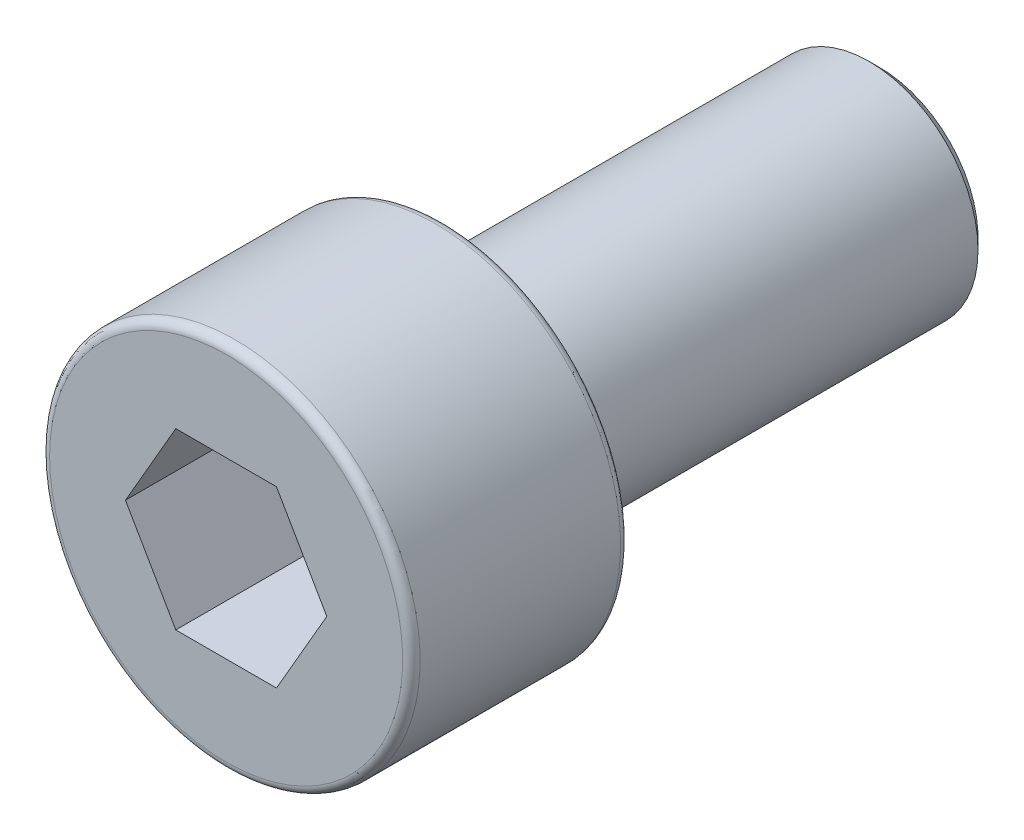
SolidWorks part; units mm, degrees
ref_plane "Front Plane" through (0, 0, 0) normal (0, 0, 1) x (1, 0, 0)
ref_plane "Top Plane" through (0, 0, 0) normal (0, 1, 0) x (1, 0, 0)
ref_plane "Right Plane" through (0, 0, 0) normal (1, 0, 0) x (0, 0, -1)
ref_plane "Plane1" through (0, 0, 15) normal (0, 0, 1) x (1, 0, 0)
sketch "Sketch1" plane through (0, 0, 15) normal (0, 0, 1) x (1, 0, 0)
  circle A0 centre (0, 0) radius 4.25
extrude "Boss-Extrude1" add sketch "Sketch1" against normal blind 5
sketch "Sketch2" plane through (0, 0, 10) normal (0, 0, -1) x (-1, 0, 0)
  circle A0 centre (0, 0) radius 2.5
extrude "Boss-Extrude2" add sketch "Sketch2" along normal blind 10
sketch "Sketch3" plane through (0, 0, 15) normal (0, 0, 1) x (1, 0, 0)
  line L0 (-2.3094, 0) -> (-1.1547, -2)
  line L1 (-1.1547, -2) -> (1.1547, -2)
  line L2 (1.1547, -2) -> (2.3094, 0)
  line L3 (2.3094, 0) -> (1.1547, 2)
  line L4 (1.1547, 2) -> (-1.1547, 2)
  line L5 (-1.1547, 2) -> (-2.3094, 0)
extrude "Cut-Extrude1" cut sketch "Sketch3" against normal blind 4
chamfer "Chamfer1" distance 0.25 angle 45 1 edges at (-2.5, 0, 0)
fillet "Fillet1" radius 0.2 2 edges at (-4.25, 0, 10) (-4.25, 0, 15) tangent propagation no
ref_axis "Axis1" through (0, 0, -2.3377) along (0, 0, 1)
